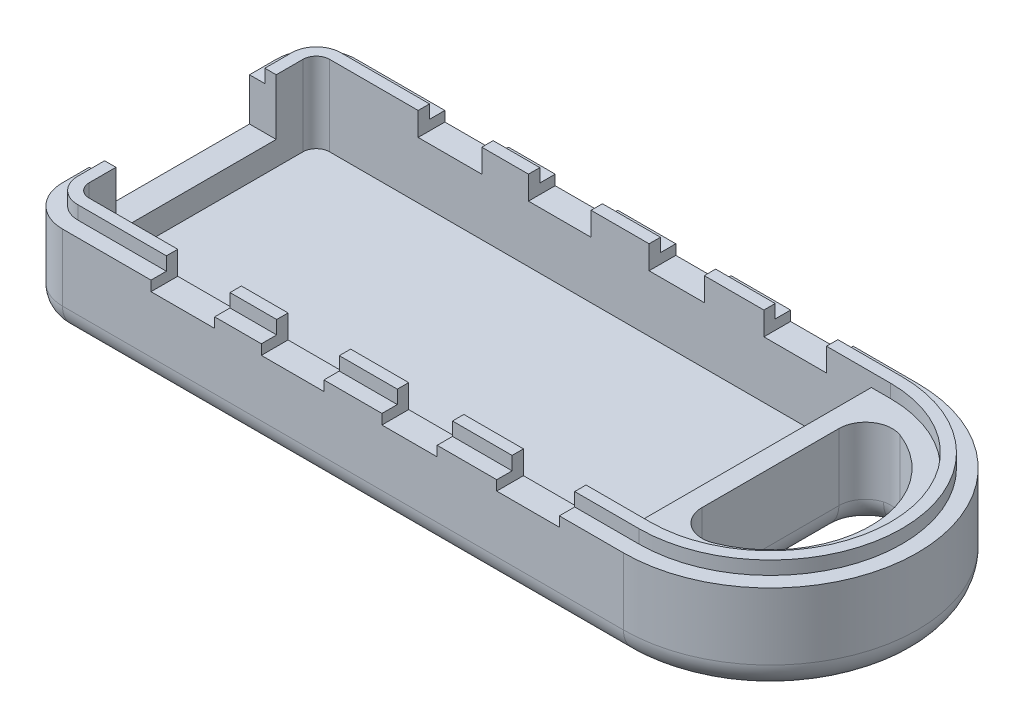
SolidWorks part; units mm, degrees
material "ABS"
ref_plane "Спереди" through (0, 0, 0) normal (0, 0, 1) x (1, 0, 0)
ref_plane "Сверху" through (0, 0, 0) normal (0, 1, 0) x (1, 0, 0)
ref_plane "Справа" through (0, 0, 0) normal (1, 0, 0) x (0, 0, -1)
sketch "Эскиз1" plane through (0, 0, 0) normal (0, 1, 0) x (1, 0, 0)
  line L0 (6.6974, 8.3377) -> (6.6974, -13.6623) construction
  line L1 (-35.3026, 8.3377) -> (6.6974, 8.3377)
  line L2 (-38.3026, 5.3377) -> (-38.3026, -10.6623)
  line L3 (-35.3026, -13.6623) -> (6.6974, -13.6623)
  arc A1 (-38.3026, -10.6623) -> (-35.3026, -13.6623) centre (-35.3026, -10.6623) ccw
  arc A2 (-38.3026, 5.3377) -> (-35.3026, 8.3377) centre (-35.3026, 5.3377) cw
  arc A4 (6.6974, 8.3377) -> (6.6974, -13.6623) centre (6.6974, -2.6623) cw
  point P6 (12.6974, -13.6623)
  point P9 (-38.3026, -13.6623)
  point P12 (-38.3026, 8.3377)
  dimension "D1" = 45
  dimension "D2" = 22
extrude "Бобышка-Вытянуть1" add sketch "Эскиз1" along normal blind 7
sketch "Эскиз2" plane through (0, 7, 0) normal (0, 1, 0) x (1, 0, 0)
  line L8 (-36.3026, 5.3377) -> (-36.3026, -10.6623)
  line L9 (-35.3026, -11.6623) -> (6.6974, -11.6623)
  line L11 (6.6974, 6.3377) -> (-35.3026, 6.3377)
  line L12 (-36.3026, 5.3377) -> (-36.3026, -10.6623)
  line L13 (-35.3026, -11.6623) -> (6.6974, -11.6623)
  line L15 (6.6974, 6.3377) -> (-35.3026, 6.3377)
  arc A3 (6.6974, -11.6623) -> (6.6974, 6.3377) centre (6.6974, -2.6623) ccw
  arc A4 (6.6974, -11.6623) -> (6.6974, 6.3377) centre (6.6974, -2.6623) ccw
  arc A8 (-35.3026, 6.3377) -> (-36.3026, 5.3377) centre (-35.3026, 5.3377) ccw
  arc A9 (-35.3026, 6.3377) -> (-36.3026, 5.3377) centre (-35.3026, 5.3377) ccw
  arc A10 (-36.3026, -10.6623) -> (-35.3026, -11.6623) centre (-35.3026, -10.6623) ccw
  arc A11 (-36.3026, -10.6623) -> (-35.3026, -11.6623) centre (-35.3026, -10.6623) ccw
  dimension "D1" = 2
extrude "Вырез-Вытянуть1" cut sketch "Эскиз2" against normal blind 5
sketch "Эскиз3" plane through (0, 2, 0) normal (0, 1, 0) x (1, 0, 0)
  line L0 (6.6974, 8.3377) -> (6.6974, -13.6623) construction
  line L5 (6.6974, 2.4612) -> (6.6974, -7.7858)
  arc A3 (9.4246, 4.3243) -> (9.4246, -9.6488) centre (6.6974, -2.6623) cw
  arc A5 (6.6974, -7.7858) -> (9.4246, -9.6488) centre (8.6974, -7.7858) ccw
  arc A6 (6.6974, 2.4612) -> (9.4246, 4.3243) centre (8.6974, 2.4612) cw
  point P11 (6.6974, -10.1623)
  point P16 (6.6974, 4.8377)
  dimension "D1" = 7.5
  dimension "D2" = 2
sketch "Эскиз4" plane through (-38.3026, 0, 0) normal (-1, 0, 0) x (0, 0, 1)
  line L0 (-3.3377, 7) -> (-3.3377, 3.8061)
  line L1 (-5.3377, 7) -> (10.6623, 7) construction
  line L2 (-3.3377, 3.8061) -> (8.6623, 3.8061)
  line L3 (8.6623, 3.8061) -> (8.6623, 7)
  line L4 (2.6623, 0) -> (2.6623, 7) construction
  line L5 (-5.3377, 0) -> (10.6623, 0) construction
  point P10 (2.6623, 3.8061)
  point P11 (-3.3377, 5.4031)
  dimension "D1" = 12
extrude "Вырез-Вытянуть3" cut sketch "Эскиз3" against normal blind 8
extrude "Вырез-Вытянуть4" cut sketch "Эскиз4" against normal blind 10 and the other way through all
sketch "Эскиз5" plane through (0, 2, 0) normal (0, 1, 0) x (1, 0, 0)
  line L1 (6.6974, 6.3377) -> (-35.3026, 6.3377) construction
  line L2 (-35.3026, -11.6623) -> (6.6974, -11.6623) construction
  line L3 (5.2536, 6.3377) -> (5.2536, -11.6623)
  line L5 (6.6974, 6.3377) -> (5.2536, 6.3377)
  line L6 (6.6974, 2.4612) -> (6.6974, -7.7858)
  line L7 (6.6974, 2.4612) -> (6.6974, -7.7858)
  line L8 (6.6974, -11.6623) -> (5.2536, -11.6623)
  arc A3 (6.6974, -11.6623) -> (6.6974, 6.3377) centre (6.6974, -2.6623) ccw
  arc A4 (6.6974, -11.6623) -> (6.6974, 6.3377) centre (6.6974, -2.6623) ccw
  arc A10 (6.6974, -7.7858) -> (9.4246, -9.6488) centre (8.6974, -7.7858) ccw
  arc A11 (9.4246, 4.3243) -> (6.6974, 2.4612) centre (8.6974, 2.4612) ccw
  arc A12 (9.4246, -9.6488) -> (9.4246, 4.3243) centre (6.6974, -2.6623) ccw
  arc A13 (6.6974, -7.7858) -> (9.4246, -9.6488) centre (8.6974, -7.7858) ccw
  arc A14 (9.4246, 4.3243) -> (6.6974, 2.4612) centre (8.6974, 2.4612) ccw
  arc A15 (9.4246, -9.6488) -> (9.4246, 4.3243) centre (6.6974, -2.6623) ccw
  dimension "D1" = 0
  dimension "D2" = 0
extrude "Бобышка-Вытянуть2" add sketch "Эскиз5" along normal blind 5
sketch "Эскиз6" plane through (0, 7, 0) normal (0, 1, 0) x (1, 0, 0)
  line L12 (-37.1526, -8.6623) -> (-37.1526, -10.6623)
  line L13 (-35.3026, -12.5123) -> (6.6974, -12.5123)
  line L14 (6.6974, 7.1877) -> (-35.3026, 7.1877)
  line L15 (-37.1526, 5.3377) -> (-37.1526, 3.3377)
  line L16 (-37.1526, -8.6623) -> (-37.1526, -10.6623)
  line L17 (-35.3026, -12.5123) -> (6.6974, -12.5123)
  line L18 (6.6974, 7.1877) -> (-35.3026, 7.1877)
  line L19 (-37.1526, 5.3377) -> (-37.1526, 3.3377)
  line L20 (-36.3026, -8.6623) -> (-37.1526, -8.6623)
  line L21 (-36.3026, 3.3377) -> (-37.1526, 3.3377)
  line L24 (-36.3026, -8.6623) -> (-36.3026, -10.6623)
  line L25 (-36.3026, 5.3377) -> (-36.3026, 3.3377)
  line L26 (6.6974, 6.3377) -> (-35.3026, 6.3377)
  line L27 (-35.3026, -11.6623) -> (6.6974, -11.6623)
  line L28 (-36.3026, -8.6623) -> (-36.3026, -10.6623)
  line L29 (-36.3026, 5.3377) -> (-36.3026, 3.3377)
  line L30 (6.6974, 6.3377) -> (-35.3026, 6.3377)
  line L31 (-35.3026, -11.6623) -> (6.6974, -11.6623)
  arc A9 (6.6974, -12.5123) -> (6.6974, 7.1877) centre (6.6974, -2.6623) ccw
  arc A10 (-37.1526, -10.6623) -> (-35.3026, -12.5123) centre (-35.3026, -10.6623) ccw
  arc A11 (-35.3026, 7.1877) -> (-37.1526, 5.3377) centre (-35.3026, 5.3377) ccw
  arc A12 (6.6974, -12.5123) -> (6.6974, 7.1877) centre (6.6974, -2.6623) ccw
  arc A13 (-37.1526, -10.6623) -> (-35.3026, -12.5123) centre (-35.3026, -10.6623) ccw
  arc A14 (-35.3026, 7.1877) -> (-37.1526, 5.3377) centre (-35.3026, 5.3377) ccw
  arc A18 (-36.3026, -10.6623) -> (-35.3026, -11.6623) centre (-35.3026, -10.6623) ccw
  arc A19 (-35.3026, 6.3377) -> (-36.3026, 5.3377) centre (-35.3026, 5.3377) ccw
  arc A20 (6.6974, -11.6623) -> (6.6974, 6.3377) centre (6.6974, -2.6623) ccw
  arc A21 (-36.3026, -10.6623) -> (-35.3026, -11.6623) centre (-35.3026, -10.6623) ccw
  arc A22 (-35.3026, 6.3377) -> (-36.3026, 5.3377) centre (-35.3026, 5.3377) ccw
  arc A23 (6.6974, -11.6623) -> (6.6974, 6.3377) centre (6.6974, -2.6623) ccw
  dimension "D1" = 1.15
  dimension "D2" = 2
extrude "Бобышка-Вытянуть3" add sketch "Эскиз6" along normal blind 1
sketch "Эскиз7" plane through (0, 0, 13.6623) normal (0, 0, 1) x (1, 0, 0)
  line L0 (-35.3026, 8) -> (6.6974, 8) construction
  line L1 (1.894, 8) -> (-2.7926, 8)
  line L2 (1.894, 8) -> (1.894, 6.261)
  line L3 (1.894, 6.261) -> (-2.7926, 6.261)
  line L4 (-2.7926, 8) -> (-2.7926, 6.261)
  line L6 (-7.2552, 8) -> (-11.3868, 8)
  line L7 (-7.2552, 8) -> (-7.2552, 6.2483)
  line L8 (-7.2552, 6.2483) -> (-11.3868, 6.2483)
  line L9 (-11.3868, 8) -> (-11.3868, 6.2483)
  line L10 (-15.7292, 8) -> (-20.4158, 8)
  line L11 (-15.7292, 8) -> (-15.7292, 6.2483)
  line L12 (-15.7292, 6.2483) -> (-20.4158, 6.2483)
  line L13 (-20.4158, 8) -> (-20.4158, 6.2483)
  line L14 (-23.9112, 8) -> (-28.6756, 8)
  line L15 (-23.9112, 8) -> (-23.9112, 6.2483)
  line L16 (-23.9112, 6.2483) -> (-28.6756, 6.2483)
  line L17 (-28.6756, 8) -> (-28.6756, 6.2483)
extrude "Вырез-Вытянуть5" cut sketch "Эскиз7" against normal through all both and the other way through all
fillet "Скругление1" radius 2 6 edges at (-37.424, 0, 12.7836) (-38.3026, 0, 2.6623) (-37.424, 0, -7.459) (-14.3026, 0, -8.3377) (17.6974, 0, 2.6623) (-14.3026, 0, 13.6623)
fillet "Скругление2" radius 2 3 edges at (7.5692, 0, 9.4372) (7.5692, 0, -4.1126) (6.6974, 0, 2.6623)
